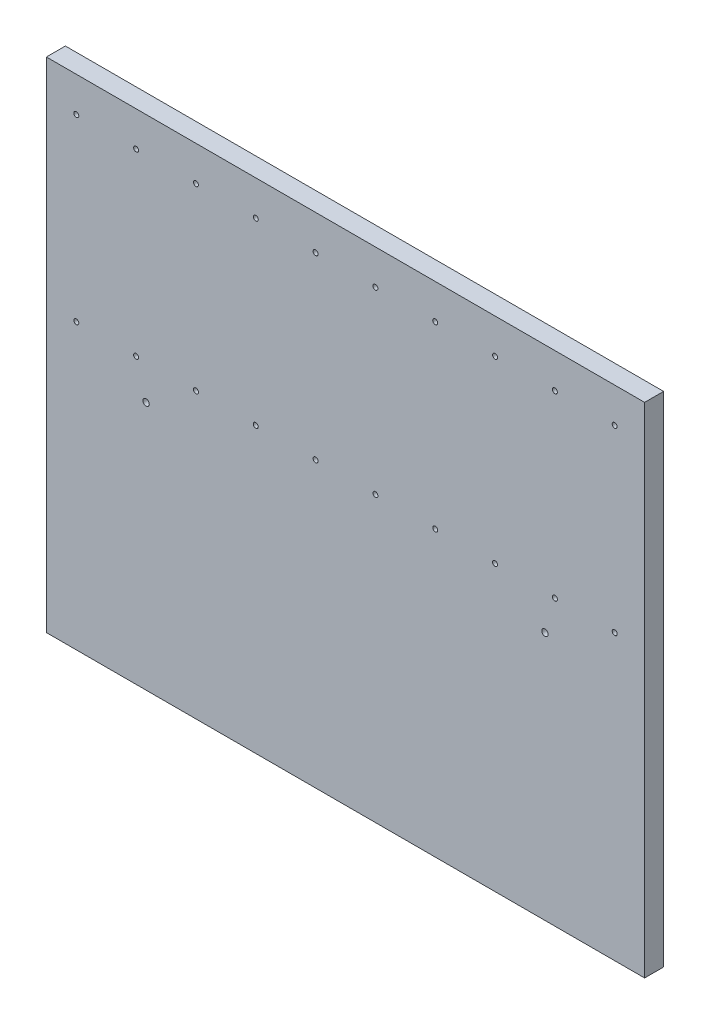
SolidWorks part; units mm, degrees
ref_plane "Front Plane" through (0, 0, 0) normal (0, 0, 1) x (1, 0, 0)
ref_plane "Top Plane" through (0, 0, 0) normal (0, 1, 0) x (1, 0, 0)
ref_plane "Right Plane" through (0, 0, 0) normal (1, 0, 0) x (0, 0, -1)
sketch "Sketch1" plane through (0, 0, 0) normal (0, 0, 1) x (1, 0, 0)
  line L0 (300, 250) -> (300, 185) construction
  line L1 (300, 250) -> (-300, 250) construction
  line L2 (300, 250) -> (300, 185)
  line L3 (300, 250) -> (-300, 250)
  line L5 (-300, -250) -> (300, -250)
  line L6 (-300, -250) -> (-300, 250)
  line L7 (-300, 250) -> (300, 250)
  line L8 (300, -250) -> (300, 250)
  dimension "D1" = 500
  dimension "D2" = 600
extrude "Boss-Extrude1" add sketch "Sketch1" along normal blind 19.05 contours L5 L8 L2 L3 L6 region at (0, 0, 0)
sketch "Sketch2" plane through (0, 0, 19.05) normal (0, 0, 1) x (1, 0, 0)
  circle A0 centre (270, 35) radius 2.5 construction
  circle A1 centre (210, 35) radius 2.5 construction
  circle A2 centre (150, 35) radius 2.5 construction
  circle A3 centre (90, 35) radius 2.5 construction
  circle A4 centre (30, 35) radius 2.5 construction
  circle A5 centre (-30, 35) radius 2.5 construction
  circle A6 centre (-90, 35) radius 2.5 construction
  circle A7 centre (-150, 35) radius 2.5 construction
  circle A8 centre (-210, 35) radius 2.5 construction
  circle A9 centre (-270, 35) radius 2.5 construction
  circle A10 centre (-270, 215) radius 2.5 construction
  circle A11 centre (-210, 215) radius 2.5 construction
  circle A12 centre (-150, 215) radius 2.5 construction
  circle A13 centre (-90, 215) radius 2.5 construction
  circle A14 centre (-30, 215) radius 2.5 construction
  circle A15 centre (30, 215) radius 2.5 construction
  circle A16 centre (90, 215) radius 2.5 construction
  circle A17 centre (150, 215) radius 2.5 construction
  circle A18 centre (210, 215) radius 2.5 construction
  circle A19 centre (270, 215) radius 2.5 construction
  circle A20 centre (270, 35) radius 2.5
  circle A21 centre (210, 35) radius 2.5
  circle A22 centre (150, 35) radius 2.5
  circle A23 centre (90, 35) radius 2.5
  circle A24 centre (30, 35) radius 2.5
  circle A25 centre (-30, 35) radius 2.5
  circle A26 centre (-90, 35) radius 2.5
  circle A27 centre (-150, 35) radius 2.5
  circle A28 centre (-210, 35) radius 2.5
  circle A29 centre (-270, 35) radius 2.5
  circle A30 centre (-270, 215) radius 2.5
  circle A31 centre (-210, 215) radius 2.5
  circle A32 centre (-150, 215) radius 2.5
  circle A33 centre (-90, 215) radius 2.5
  circle A34 centre (-30, 215) radius 2.5
  circle A35 centre (30, 215) radius 2.5
  circle A36 centre (90, 215) radius 2.5
  circle A37 centre (150, 215) radius 2.5
  circle A38 centre (210, 215) radius 2.5
  circle A39 centre (270, 215) radius 2.5
extrude "Cut-Extrude1" cut sketch "Sketch2" against normal blind 5
sketch "Sketch3" plane through (0, 0, 19.05) normal (0, 0, 1) x (1, 0, 0)
  circle A0 centre (-200, 0) radius 3.175
  circle A1 centre (200, 0) radius 3.175
extrude "Cut-Extrude2" cut sketch "Sketch3" against normal through all
